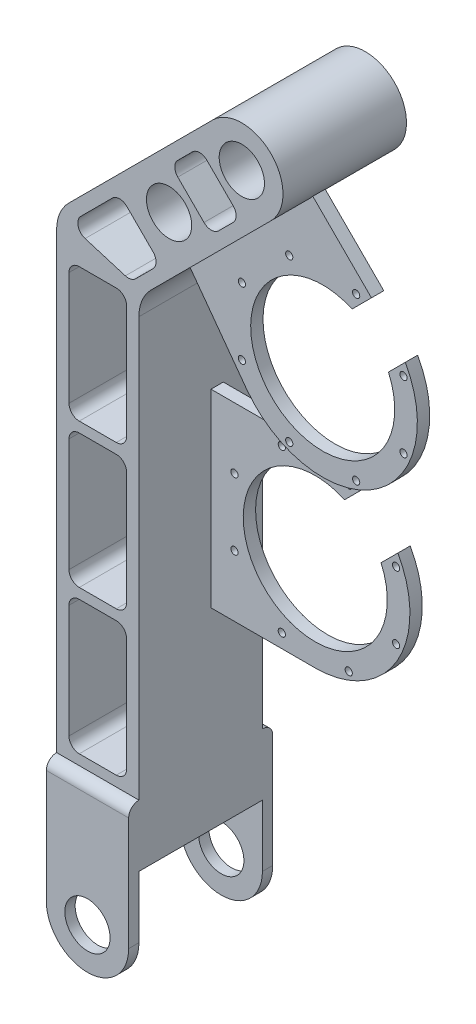
SolidWorks part; units mm, degrees
material "6061 合金"
ref_plane "前视基准面" through (0, 0, 0) normal (0, 0, 1) x (1, 0, 0)
ref_plane "上视基准面" through (0, 0, 0) normal (0, 1, 0) x (1, 0, 0)
ref_plane "右视基准面" through (0, 0, 0) normal (1, 0, 0) x (0, 0, -1)
other "Configuration Table"
sketch "草图1" plane through (0, 0, 0) normal (0, 0, 1) x (1, 0, 0)
  circle A0 centre (0, 0) radius 20
  circle A1 centre (0, 0) radius 11
  dimension "D1" = 40
  dimension "D2" = 22
extrude "凸台-拉伸1" add sketch "草图1" along normal blind 60 contours A1 | A0 region at (0, 0, 0)
ref_plane "基准面1" through (0, 0, 30) normal (0, 0, 1) x (1, 0, 0)
sketch "草图2" plane through (0, 0, 30) normal (0, 0, 1) x (1, 0, 0)
  line L0 (0, 0) -> (-70, -70) construction
  line L1 (-70, -70) -> (-70, -320) construction
  line L2 (0, -57.3148) -> (0, 49.9409) construction
  line L3 (-56.8582, 0) -> (46.4003, 0) construction
  line L4 (-14.1421, 14.1421) -> (-90, -61.7157)
  line L5 (14.1421, -14.1421) -> (-50, -78.2843)
  line L6 (-90, -61.7157) -> (-90, -320)
  line L7 (-50, -78.2843) -> (-50, -320)
  line L8 (-90, -320) -> (-50, -320)
  circle A2 centre (0, 0) radius 20 construction
  arc A3 (-14.1421, 14.1421) -> (14.1421, -14.1421) centre (0, 0) ccw
  dimension "D1" = 45
  dimension "D2" = 250
  dimension "D3" = 70
  dimension "D4" = 40
  dimension "D5" = 40
extrude "凸台-拉伸2" add sketch "草图2" along normal mid plane 60 contours L7 L8 L6 L4 A3 L5
sketch "草图4" plane through (0, 0, 60) normal (0, 0, 1) x (1, 0, 0)
  line L0 (-90, -61.7157) -> (-90, -320) construction
  line L1 (-90, -290) -> (-50, -290)
  line L2 (-90, -290) -> (-90, -350)
  line L4 (-50, -290) -> (-50, -350)
  line L5 (-50, -78.2843) -> (-50, -320) construction
  line L6 (-90, -320) -> (-50, -320) construction
  arc A0 (-90, -350) -> (-50, -350) centre (-70, -350) ccw
  circle A1 centre (-70, -350) radius 11
  dimension "D3" = 22
  dimension "D1" = 30
  dimension "D2" = 30
extrude "凸台-拉伸3" add sketch "草图4" along normal blind 5
mirror "镜向1" about plane through (0, 0, 30) normal (0, 0, 1) of "凸台-拉伸3"
sketch "草图5" plane through (0, 0, 0) normal (0, 1, 0) x (1, 0, 0)
  line L0 (0, 0) -> (0, -78.0582) construction
ref_plane "基准面2" through (-70, 0, 0) normal (-1, 0, 0) x (0, 0, 1)
sketch "草图7" plane through (-70, 0, 0) normal (-1, 0, 0) x (0, 0, 1)
  line L0 (-34.1239, -350) -> (109.535, -350) construction
sketch "草图8" plane through (0, 0, 60) normal (0, 0, 1) x (1, 0, 0)
  line L0 (0, 0) -> (-70, -70) construction
  circle A0 centre (-35.3553, -35.3553) radius 11
  dimension "D1" = 22
  dimension "D2" = 50
extrude "切除-拉伸1" cut sketch "草图8" against normal blind 100
fillet "圆角4" radius 20 2 edges at (-90, -61.7157, 30) (-50, -78.2843, 30)
fillet "圆角1" [suppressed] radius 50
fillet "圆角2" [suppressed] radius 3
sketch "草图9" plane through (0, 0, 65) normal (0, 0, 1) x (1, 0, 0)
  circle A0 centre (-70, -350) radius 13
  dimension "D1" = 26
extrude "切除-拉伸2" [suppressed] cut sketch "草图9" against normal blind 0.75
sketch "草图10" plane through (0, 0, -5) normal (0, 0, -1) x (-1, 0, 0)
  circle A0 centre (70, -350) radius 13
  dimension "D1" = 26
extrude "切除-拉伸3" [suppressed] cut sketch "草图10" against normal blind 0.75 contours A0
sketch "草图11" plane through (-90, 0, 0) normal (-1, 0, 0) x (0, 0, 1)
  circle A0 centre (48.5, -118.9949) radius 2.75
  circle A1 centre (48.5, -183.9949) radius 2.75
  circle A2 centre (48.5, -248.9949) radius 2.75
  circle A3 centre (11.5, -248.9949) radius 2.75
  circle A4 centre (11.5, -183.9949) radius 2.75
  circle A5 centre (11.5, -118.9949) radius 2.75
  dimension "D1" = 5.5
extrude "切除-拉伸4" [suppressed] cut sketch "草图11" against normal through all contours A1 | A2 | A0 | A3 | A4 | A5
sketch "草图12" [suppressed] plane through (-90, 0, 0) normal (-1, 0, 0) x (0, 0, 1)
  line L0 (30, -62.0134) -> (30, -339.6946) construction
  line L1 (10, -128.9949) -> (50, -128.9949)
  line L2 (10, -128.9949) -> (10, -173.9949)
  line L3 (10, -173.9949) -> (50, -173.9949)
  line L4 (50, -128.9949) -> (50, -173.9949)
  line L5 (10, -193.9949) -> (50, -193.9949)
  line L6 (10, -193.9949) -> (10, -238.9949)
  line L7 (10, -238.9949) -> (50, -238.9949)
  line L8 (50, -193.9949) -> (50, -238.9949)
  line L9 (10, -258.9949) -> (50, -258.9949)
  line L10 (10, -258.9949) -> (10, -290)
  line L11 (10, -290) -> (50, -290)
  line L12 (50, -258.9949) -> (50, -290)
  line L13 (19.5, -173.9949) -> (40.5, -173.9949)
  line L14 (19.5, -173.9949) -> (19.5, -193.9949)
  line L15 (19.5, -193.9949) -> (40.5, -193.9949)
  line L16 (40.5, -173.9949) -> (40.5, -193.9949)
  line L17 (19.5, -238.9949) -> (40.5, -238.9949)
  line L18 (19.5, -238.9949) -> (19.5, -258.9949)
  line L19 (19.5, -258.9949) -> (40.5, -258.9949)
  line L20 (40.5, -238.9949) -> (40.5, -258.9949)
  line L21 (60, -82.4264) -> (60, -290) construction
  line L22 (0, -290) -> (0, -82.4264) construction
  line L23 (57, -320) -> (3, -320) construction
  circle A0 centre (48.5, -118.9949) radius 2.75 construction
  circle A1 centre (48.5, -183.9949) radius 2.75 construction
  circle A2 centre (48.5, -248.9949) radius 2.75 construction
  dimension "D1" = 10
  dimension "D2" = 10
  dimension "D3" = 10
  dimension "D4" = 8
  dimension "D5" = 10
  dimension "D6" = 10
  dimension "D7" = 10
  dimension "D8" = 30
extrude "减重" [suppressed] cut sketch "草图12" against normal through all contours L0 L1 L2 L3 | L15 L0 L17 L7 L8 L5 | L0 L5 L6 L7 | L19 L0 L11 L12 L9 | L0 L9 L10 L11 | L1 L0 L13 L3 L4
fillet "圆角3" [suppressed] radius 3
sketch "草图13" plane through (0, 0, 60) normal (0, 0, 1) x (1, 0, 0)
  circle A0 centre (0, 0) radius 13
  circle A1 centre (-35.3553, -35.3553) radius 13
  dimension "D1" = 26
  dimension "D2" = 26
extrude "切除-拉伸6" [suppressed] cut sketch "草图13" against normal blind 1.75
sketch "草图14" plane through (0, 0, 0) normal (0, 0, -1) x (-1, 0, 0)
  circle A0 centre (0, 0) radius 13
  circle A1 centre (35.3553, -35.3553) radius 13
  dimension "D1" = 26
  dimension "D2" = 26
extrude "切除-拉伸7" [suppressed] cut sketch "草图14" against normal blind 1.75
sketch "草图15" [suppressed] plane through (0, 0, 0) normal (0, 0, -1) x (-1, 0, 0)
  line L0 (0, 0) -> (70, -350) construction
  line L1 (56.2719, -67.2005) -> (60.1942, -86.8121) construction
  line L2 (70, -350) -> (204.3541, -323.1292) construction
  circle A0 centre (56.2719, -67.2005) radius 2.75
  circle A1 centre (75.2172, -73.6095) radius 2.75
  circle A2 centre (60.1942, -86.8121) radius 2.75
  dimension "D1" = 5.5
  dimension "D2" = 20
  dimension "D3" = 20
  dimension "D4" = 20
  dimension "D5" = 42
  dimension "D6" = 270
extrude "切除-拉伸8" [suppressed] cut sketch "草图15" against normal through all contours A2 | A0 | A1
ref_plane "小腿主干连杆面" through (0, 0, 0) normal (0.9806, -0.1961, 0) x (0, 0, -1)
ref_plane "小腿主干对称面" through (0, 0, 30) normal (0, 0, -1) x (-1, 0, 0)
sketch "草图16" plane through (0, 0, 60) normal (0, 0, 1) x (1, 0, 0)
  line L0 (0, 0) -> (-70, -350)
  line L1 (-35.3553, -35.3553) -> (0, 0)
sketch "草图17" plane through (0, 0, 60) normal (0, 0, 1) x (1, 0, 0)
  line L0 (0, 0) -> (-70, -350) construction
  line L1 (118.6974, 32.5948) -> (32.9122, -396.3312) construction
  line L2 (92.7764, -97.0102) -> (20.2919, -82.5133)
  line L3 (73.1648, -195.0683) -> (0.6803, -180.5713)
  circle A0 centre (20.2919, -82.5133) radius 46
  circle A1 centre (0.6803, -180.5713) radius 46
  dimension "D3" = 92
  dimension "D4" = 92
  dimension "D1" = 110
  dimension "D2" = 73.92
  dimension "D5" = 180
  dimension "D6" = 280
sketch "草图18" plane through (0, 0, 60) normal (0, 0, 1) x (1, 0, 0)
  line L0 (-44.1421, -72.4264) -> (-16.8058, -109.7119)
  line L1 (14.1421, -14.1421) -> (-44.1421, -72.4264) construction
  line L3 (14.1421, -14.1421) -> (-44.1421, -72.4264)
  line L4 (15.4873, -12.6548) -> (52.8188, -49.9864)
  line L10 (-90, -290) -> (-50, -290)
  line L11 (-50, -290) -> (-50, -86.5685)
  line L12 (-44.1421, -72.4264) -> (14.1421, -14.1421)
  line L13 (-14.1421, 14.1421) -> (-84.1421, -55.8579)
  line L14 (-90, -70) -> (-90, -290)
  line L17 (-44.1421, -72.4264) -> (14.1421, -14.1421)
  circle A0 centre (20.2919, -82.5133) radius 46 construction
  arc A1 (14.1421, -14.1421) -> (-14.1421, 14.1421) centre (0, 0) ccw construction
  arc A2 (14.1421, -14.1421) -> (-14.1421, 14.1421) centre (0, 0) ccw
  arc A3 (14.1421, -14.1421) -> (15.4873, -12.6548) centre (0, 0) ccw
  arc A4 (-16.8058, -109.7119) -> (52.8188, -49.9864) centre (20.2919, -82.5133) ccw
  circle A5 centre (20.2919, -82.5133) radius 35
  arc A9 (-84.1421, -55.8579) -> (-90, -70) centre (-70, -70) ccw
  arc A11 (-44.1421, -72.4264) -> (-50, -86.5685) centre (-30, -86.5685) ccw
  point P19 (10.7418, -127.511)
  line M14 (-50, -290) -> (-50, -86.5685)
  line M15 (-44.1421, -72.4264) -> (14.1421, -14.1421)
  arc M16 (14.1421, -14.1421) -> (-14.1421, 14.1421) centre (0, 0) ccw
  arc M22 (-50, -86.5685) -> (-44.1421, -72.4264) centre (-30, -86.5685) cw
  dimension "D2" = 70
  dimension "D1" = 0
extrude "凸台-拉伸4" add sketch "草图18" against normal blind 6 from offset 19 contours A4 L4 A5 M16 M15 M22 M14 region at (-13.8682, -44.4161, 60) offset against normal yes
sketch "草图19" plane through (0, 0, 0) normal (0, 0, -1) x (-1, 0, 0)
  line L0 (50, -86.5685) -> (50, -290) construction
  line L1 (50, -134.5713) -> (50, -226.5713)
  line L2 (-0.6803, -134.5713) -> (50, -134.5713)
  line L3 (-0.6803, -226.5713) -> (50, -226.5713)
  circle A0 centre (-0.6803, -180.5713) radius 46 construction
  arc A1 (-0.6803, -134.5713) -> (-0.6803, -226.5713) centre (-0.6803, -180.5713) ccw
  circle A2 centre (-0.6803, -180.5713) radius 35
  dimension "D1" = 70
extrude "凸台-拉伸5" add sketch "草图19" against normal blind 6 from offset 19 offset against normal yes
sketch "草图21" plane through (0, 0, 65) normal (0, 0, 1) x (1, 0, 0)
  line L0 (-70, -350) -> (-70, -6.9331) construction
  circle A0 centre (-70, -75) radius 2.6
  circle A1 centre (-70, -250) radius 2.6
  circle A2 centre (-58, -300) radius 2.6
  circle A3 centre (-82, -300) radius 2.6
  dimension "D1" = 5.2
  dimension "D2" = 12
  dimension "D3" = 50
  dimension "D4" = 100
  dimension "D5" = 175
extrude "切除-拉伸9" [suppressed] cut sketch "草图21" against normal through all both and the other way through all
sketch "草图22" plane through (0, 0, 41) normal (0, 0, 1) x (1, 0, 0)
  line L0 (20.2919, -12.4618) -> (20.2919, -82.5133) construction
  line L1 (0.6803, -180.5713) -> (0.6803, -131.6862) construction
  circle A0 centre (20.2919, -82.5133) radius 42.5 construction
  circle A1 centre (36.5559, -43.2484) radius 1.75
  circle A2 centre (59.5567, -66.2492) radius 1.75
  circle A3 centre (59.5567, -98.7773) radius 1.75
  circle A4 centre (36.5559, -121.7782) radius 1.75
  circle A5 centre (4.0278, -121.7782) radius 1.75
  circle A6 centre (-18.973, -98.7773) radius 1.75
  circle A7 centre (-18.973, -66.2492) radius 1.75
  circle A8 centre (4.0278, -43.2484) radius 1.75
  circle A9 centre (0.6803, -180.5713) radius 42.5 construction
  circle A10 centre (16.9443, -141.3065) radius 1.75
  circle A11 centre (39.9451, -164.3073) radius 1.75
  circle A12 centre (39.9451, -196.8354) radius 1.75
  circle A13 centre (16.9443, -219.8362) radius 1.75
  circle A14 centre (-15.5838, -219.8362) radius 1.75
  circle A15 centre (-38.5846, -196.8354) radius 1.75
  circle A16 centre (-38.5846, -164.3073) radius 1.75
  circle A17 centre (-15.5838, -141.3065) radius 1.75
  point P22 (20.2919, -82.5133)
  point P28 (0.6803, -180.5713)
  point P43 (0.6803, -180.5713)
  dimension "D1" = 85
  dimension "D2" = 3.5
  dimension "D4" = 85
  dimension "D5" = 3.5
  dimension "D3" = 8
  dimension "D6" = 8
extrude "切除-拉伸10" cut sketch "草图22" against normal up to surface (22 mm away) up to face at (-34.3197, -180.5713, 19)
sketch "草图23" plane through (0, 0, 60) normal (0, 0, 1) x (1, 0, 0)
  line L0 (-90, -70) -> (-90, -290) construction
  line L1 (-84, -220) -> (-56, -220)
  line L2 (-84, -220) -> (-84, -285)
  line L3 (-84, -285) -> (-56, -285)
  line L4 (-56, -220) -> (-56, -285)
  line L5 (-84, -150) -> (-56, -150)
  line L6 (-84, -150) -> (-84, -215)
  line L7 (-84, -215) -> (-56, -215)
  line L8 (-56, -150) -> (-56, -215)
  line L9 (-84, -80) -> (-56, -80)
  line L10 (-84, -80) -> (-84, -145)
  line L11 (-84, -145) -> (-56, -145)
  line L12 (-56, -80) -> (-56, -145)
  line L13 (-50, -86.5685) -> (-50, -290) construction
  line L14 (-50, -290) -> (-90, -290) construction
  line L15 (-59.397, -39.598) -> (-84.1457, -64.3467)
  line L16 (-84.1457, -64.3467) -> (-53.7401, -73.5391)
  line L17 (-53.7401, -73.5391) -> (-39.598, -59.397)
  line L18 (-39.598, -59.397) -> (-59.397, -39.598)
  line L19 (-14.1421, 14.1421) -> (-84.1421, -55.8579) construction
  line L20 (-44.1421, -72.4264) -> (14.1421, -14.1421) construction
  line L21 (-20.5061, -0.7071) -> (-34.6482, -14.8492)
  line L22 (-34.6482, -14.8492) -> (-14.8492, -34.6482)
  line L23 (-14.8492, -34.6482) -> (-0.7071, -20.5061)
  line L24 (-0.7071, -20.5061) -> (-20.5061, -0.7071)
  point P33 (-20.6109, -26.2949)
  dimension "D1" = 5
  dimension "D2" = 6
  dimension "D3" = 6
  dimension "D4" = 5
  dimension "D5" = 5
  dimension "D6" = 65
  dimension "D7" = 65
  dimension "D8" = 65
  dimension "D9" = 70
  dimension "D10" = 6
  dimension "D11" = 6
  dimension "D12" = 20
  dimension "D13" = 35
  dimension "D14" = 6
  dimension "D15" = 6
  dimension "D16" = 15
  dimension "D17" = 35
extrude "切除-拉伸11" cut sketch "草图23" along direction (0, 0, 1) on the side against the normal up to surface (60 mm away) up to face at (-24.3553, -35.3553, 0)
fillet "圆角6" radius 5 22 edges at (-70, -290, -5) (-70, -290, 65) (-84, -285, 30) (-56, -285, 30) (-56, -220, 30) (-84, -220, 30) (-84, -215, 30) (-56, -215, 30) (-84, -150, 30) (-56, -150, 30) (-84, -145, 30) (-56, -145, 30) (-84, -80, 30) (-56, -80, 30) (-53.7401, -73.5391, 30) (-39.598, -59.397, 30) (-59.397, -39.598, 30) (-84.1457, -64.3467, 30) (-20.5061, -0.7071, 30) (-34.6482, -14.8492, 30) (-14.8492, -34.6482, 30) (-0.7071, -20.5061, 30)
sketch "草图25" plane through (0, 0, 41) normal (0, 0, 1) x (1, 0, 0)
  line L0 (20.2919, -82.5133) -> (67.3476, -35.4576) construction
  line L1 (31.1853, -53.9422) -> (48.863, -71.6198)
  line L2 (48.863, -71.6198) -> (68.0198, -52.463)
  line L3 (68.0198, -52.463) -> (50.3422, -34.7853)
  line L4 (50.3422, -34.7853) -> (31.1853, -53.9422)
  line L5 (0.6803, -180.5713) -> (50.2543, -130.9973) construction
  line L6 (9.2203, -154.3536) -> (26.898, -172.0313)
  line L7 (26.898, -172.0313) -> (46.6, -152.3293)
  line L8 (46.6, -152.3293) -> (28.9223, -134.6516)
  line L9 (28.9223, -134.6516) -> (9.2203, -154.3536)
  circle A0 centre (59.5567, -66.2492) radius 1.75 construction
  circle A1 centre (36.5559, -43.2484) radius 1.75 construction
  circle A2 centre (39.9451, -164.3073) radius 1.75 construction
  circle A3 centre (16.9443, -141.3065) radius 1.75 construction
  dimension "D1" = 25
  dimension "D2" = 25
extrude "切除-拉伸12" cut sketch "草图25" against normal up to surface (22 mm away) up to face at (15.1943, -141.3065, 19)
